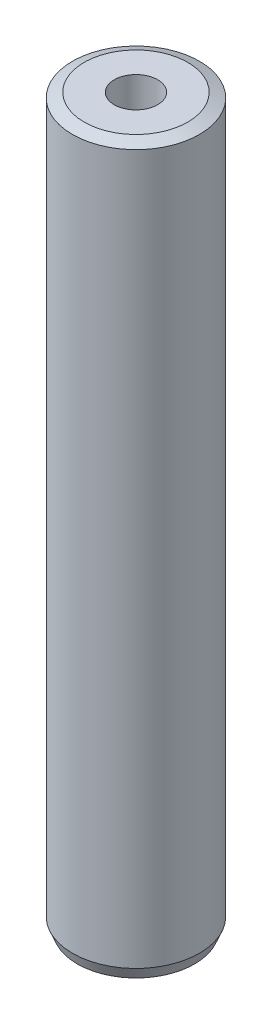
SolidWorks part; units mm, degrees
ref_plane "Front Plane" through (0, 0, 0) normal (0, 0, 1) x (1, 0, 0)
ref_plane "Top Plane" through (0, 0, 0) normal (0, 1, 0) x (1, 0, 0)
ref_plane "Right Plane" through (0, 0, 0) normal (1, 0, 0) x (0, 0, -1)
sketch "Sketch1" plane through (0, 0, 0) normal (0, 1, 0) x (1, 0, 0)
  circle A0 centre (0, 0) radius 52.5
  dimension "SHAFT_OD" = 105
extrude "Boss-Extrude1" add sketch "Sketch1" along normal blind 600
sketch "Sketch2" plane through (0, 0, 0) normal (0, 1, 0) x (1, 0, 0)
  circle A0 centre (0, 0) radius 17.9358
  dimension "BORE_D" = 35.8716
extrude "Cut-Extrude1" cut sketch "Sketch2" along normal through all
chamfer "Chamfer1" distance 4.0083 angle 67.524 2 edges at (0, 600, 52.5) (0, 0, 52.5) first distance on face at (0, 600, 52.5) first distance on face at (0, 0, 17.9358)
